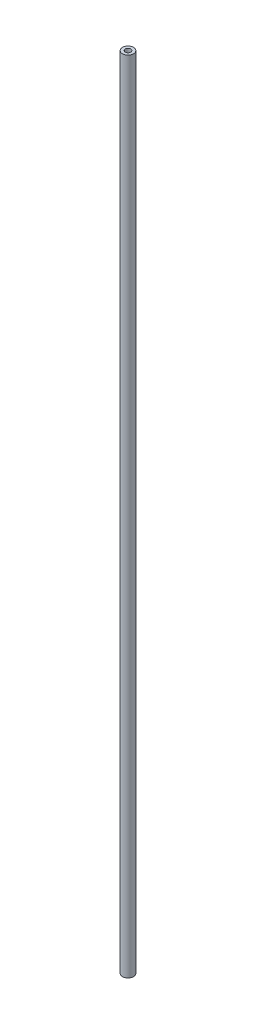
SolidWorks part; units mm, degrees
ref_plane "Front Plane" through (0, 0, 0) normal (0, 0, 1) x (1, 0, 0)
ref_plane "Top Plane" through (0, 0, 0) normal (0, 1, 0) x (1, 0, 0)
ref_plane "Right Plane" through (0, 0, 0) normal (1, 0, 0) x (0, 0, -1)
sketch "Sketch1" plane through (0, 0, 0) normal (0, 1, 0) x (1, 0, 0)
  circle A0 centre (0, 0) radius 6.35
  circle A1 centre (0, 0) radius 3.175
  dimension "D2" = 12.7
  dimension "D1" = 3.175
extrude "Boss-Extrude1" add sketch "Sketch1" along normal blind 914.4
equation "\"Pstrut_L\"= 36in"
equation "\"Pstrut_D\"= 1in"
equation "\"Pstrut_T\"= 0.25"
equation "\"Sstrut_L\"= 36in"
equation "\"Sstrut_D\"= 0.5in"
equation "\"Sstrut_T\"= 0.125"
equation "\"Dstrut_L\"= 10in"
equation "\"Dstrut_D\"= 0.5in"
equation "\"Dstrut_T\"= 0.125"
equation "\"D1@Sketch1\"=\"Sstrut_T\""
equation "\"D2@Sketch1\"=\"Sstrut_D\""
equation "\"D1@Boss-Extrude1\"=\"Sstrut_L\""
